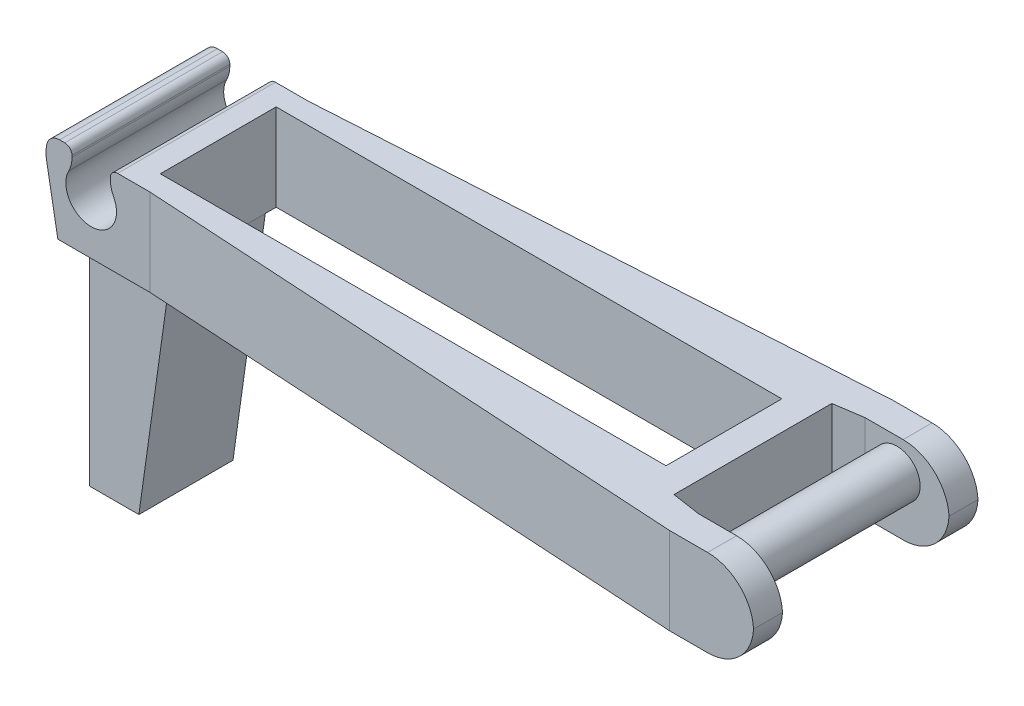
SolidWorks part; units mm, degrees
ref_plane "Front Plane" through (0, 0, 0) normal (0, 0, 1) x (1, 0, 0)
ref_plane "Top Plane" through (0, 0, 0) normal (0, 1, 0) x (1, 0, 0)
ref_plane "Right Plane" through (0, 0, 0) normal (1, 0, 0) x (0, 0, -1)
sketch "Sketch1" plane through (0, 0, 0) normal (0, 0, 1) x (1, 0, 0)
  line L0 (-24.05, 2.354) -> (-24.4097, 2.354)
  line L1 (-18.725, 2.354) -> (-20.4, 2.354)
  line L2 (-22.225, 0) -> (22.225, 0) construction
  line L3 (22.225, 0) -> (22.225, 0.15) construction
  line L4 (-23.55, 1.734) -> (-23.55, 1.854)
  line L5 (-20.9, 1.734) -> (-20.9, 1.854)
  line L6 (-24.525, -3.6477) -> (-25.3059, 0.6714)
  line L7 (-24.525, -3.6477) -> (18.025, -3.6477)
  line L8 (18.025, -3.6477) -> (18.025, 2.354)
  line L9 (18.025, 2.354) -> (-18.725, 2.354)
  line L10 (20.625, 0.15) -> (18.025, 0.15) construction
  arc A0 (-24.4097, 2.354) -> (-25.2894, 1.6441) centre (-24.4097, 1.454) ccw
  arc A1 (-20.4, 2.354) -> (-20.9, 1.854) centre (-20.4, 1.854) ccw
  arc A2 (-20.9, 1.734) -> (-20.6733, 0.8092) centre (-18.9, 1.734) ccw
  arc A3 (-23.55, 1.854) -> (-24.05, 2.354) centre (-24.05, 1.854) ccw
  arc A4 (-23.7767, 0.8092) -> (-23.55, 1.734) centre (-25.55, 1.734) ccw
  arc A5 (-23.7767, 0.8092) -> (-20.6733, 0.8092) centre (-22.225, 0) ccw
  arc A6 (20.625, 0.15) -> (21.4375, -1.2428) centre (22.225, 0.15) ccw
  arc A7 (21.4276, 1.5372) -> (20.625, 0.15) centre (22.225, 0.15) ccw
  arc A8 (21.4375, -1.2428) -> (21.4276, 1.5372) centre (22.225, 0.15) ccw
  arc A9 (-25.2894, 1.6441) -> (-25.3059, 0.6714) centre (-22.8458, 1.1162) ccw
  point P4 (0, 0)
  point P24 (0, 0)
  point P31 (-7.5299, 0)
  point P32 (18.292, -3.6477)
  point P33 (0, 0)
  point P41 (0, 0)
  dimension "D1" = 1.75
  dimension "D2" = 1.6
  dimension "D4" = 0.5
  dimension "D6" = 2.5
  dimension "D10" = 0.9
  dimension "D3" = 0.12
  dimension "D5" = 1.675
  dimension "D7" = 4.3891
  dimension "D8" = 79.751
  dimension "D9" = 0.979
  dimension "D11" = 1.2223
  dimension "D12" = 0.3597
  dimension "D13" = 0.8797
  dimension "D14" = 0.8092
  dimension "D15" = 0.9248
  dimension "D16" = 0.15
  dimension "D17" = 2.6
  dimension "D18" = 6.0017
  dimension "D19" = 44.45
extrude "Boss-Extrude1" add sketch "Sketch1" along normal mid plane 10.9 contours A6 A8 A7 | L7 L8 L9 L1 A1 L5 A2 A5 A4 L4 A3 L0 A0 A9 L6 region at (22.225, 0.15, 0)
extrude "Boss-Extrude2" add sketch "Sketch1<4>" along normal mid plane 11.5 contours A8 A7 A6
sketch "Sketch1<4>" plane through (0, 0, 0) normal (0, 0, 1) x (1, 0, 0) same geometry as "Sketch1"
sketch "Sketch2" plane through (0, -3.6477, 0) normal (0, -1, 0) x (-1, 0, 0)
  line L0 (-25.825, 5.75) -> (-20.0177, 5.75)
  line L1 (-20.625, 5.75) -> (-23.825, 5.75) construction
  line L2 (-23.825, 5.75) -> (-23.825, -5.75) construction
  line L3 (-25.825, 5.75) -> (-25.825, 7.75)
  line L4 (-25.825, 7.75) -> (-20.0177, 7.75)
  line L5 (18.175, -5.45) -> (18.175, 5.45)
  line L7 (18.175, 5.45) -> (-20.0177, 7.75)
  line L8 (-20.0177, 5.75) -> (-18.025, 5.45)
  line L9 (-18.025, 5.45) -> (18.175, 0)
  line L10 (18.175, 0) -> (-30.5676, 0) construction
  line L11 (-18.025, -5.45) -> (18.175, 0)
  line L12 (-20.0177, -5.75) -> (-18.025, -5.45)
  line L13 (18.175, -5.45) -> (-20.0177, -7.75)
  line L14 (-25.825, -7.75) -> (-20.0177, -7.75)
  line L15 (-25.825, -5.75) -> (-25.825, -7.75)
  line L16 (-25.825, -5.75) -> (-20.0177, -5.75)
  line L18 (24.525, 5.45) -> (-18.025, 5.45) construction
  line L19 (24.525, -5.45) -> (24.525, 5.45) construction
  line L20 (24.525, -5.45) -> (-18.025, -5.45) construction
  point P11 (15.1799, -5.45)
  point P12 (18.6826, 5.45)
  point P23 (20.6733, 5.45)
  point P25 (20.6733, 5.45)
  point P29 (18.175, 5.45)
  point P30 (18.175, 0.8709)
  point P31 (0, 0)
  line M9 (24.525, 5.45) -> (-18.025, 5.45)
  line M11 (-18.025, -5.45) -> (24.525, -5.45)
  dimension "D1" = 2
  dimension "D2" = 2
  dimension "D3" = 6.35
extrude "Boss-Extrude3" add sketch "Sketch2" against normal up to surface (6.0017 mm away) contours L9 L5 M9 | L0 L8 L7 L4 L3 M9 | L11 L5 M11 | L16 L15 L14 L13 L12 M11 region at (10.5089, -3.6477, -6.3324) region at (-6.1083, -3.6477, 3.6333) region at (-6.1083, -3.6477, -3.6333) region at (10.5089, -3.6477, 6.3324) up to face at (-1.1875, 2.354, 0)
fillet "Fillet1" radius 3.175 4 edges at (25.825, 2.354, -6.75) (25.825, -3.6477, -6.75) (25.825, 2.354, 6.75) (25.825, -3.6477, 6.75)
sketch "Sketch3" plane through (0, -3.6477, 0) normal (0, -1, 0) x (-1, 0, 0)
  line L0 (24.525, -5.45) -> (24.525, 5.45) construction
  line L1 (18.9, -4) -> (-16.025, -4)
  line L2 (18.9, -4) -> (18.9, 4)
  line L3 (18.9, 4) -> (-16.025, 4)
  line L4 (-16.025, -4) -> (-16.025, 4)
  line L6 (-18.025, -5.45) -> (-18.025, 5.45) construction
  point P8 (18.9, 0)
  point P9 (24.525, 0)
  dimension "D1" = 8
  dimension "D2" = 34.925
  dimension "D3" = 2
extrude "Cut-Extrude1" cut sketch "Sketch3" against normal through all contours L2 L3 L4 L1
sketch "Sketch4" plane through (0, 0, 0) normal (0, 0, 1) x (1, 0, 0)
  line L0 (-18.9, -3.6477) -> (-21.1311, -19.5227)
  line L1 (-24.525, -3.6477) -> (-18.175, -3.6477) construction
  line L2 (-21.1311, -19.5227) -> (-24.525, -19.5227)
  line L3 (-24.525, -19.5227) -> (-24.525, -3.6477)
  line L4 (-24.525, -3.6477) -> (-18.9, -3.6477)
  point P7 (-18.937, -3.6477)
  point P8 (-21.1514, -19.5227)
  point P9 (0, 0)
  dimension "D2" = 15.875
  dimension "D3" = 8
extrude "Boss-Extrude5" add sketch "Sketch4" along normal mid plane 6.5
